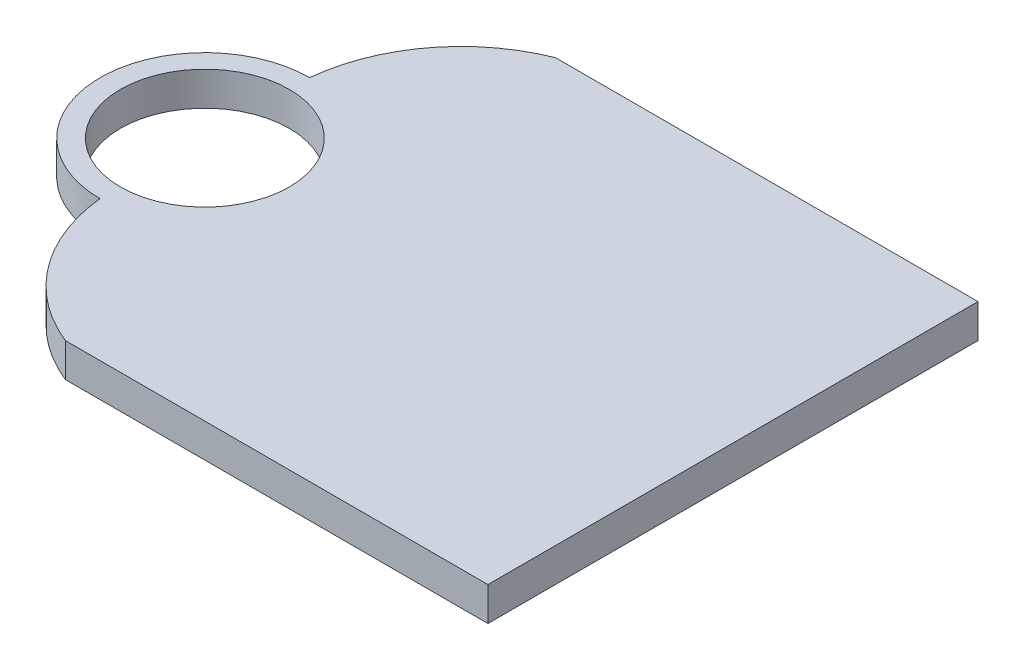
SolidWorks part; units mm, degrees
ref_plane "Front Plane" through (0, 0, 0) normal (0, 0, 1) x (1, 0, 0)
ref_plane "Top Plane" through (0, 0, 0) normal (0, 1, 0) x (1, 0, 0)
ref_plane "Right Plane" through (0, 0, 0) normal (1, 0, 0) x (0, 0, -1)
sketch "Sketch1" plane through (0, -22.822, 0) normal (0, 1, 0) x (1, 0, 0)
  line L0 (12.5, -29) -> (62.5, -29)
  line L1 (12.5, 0) -> (62.5, 0) construction
  line L2 (12.5, -29) -> (12.5, 29) construction
  line L3 (12.5, 29) -> (62.5, 29)
  line L4 (62.5, -29) -> (62.5, 29)
  line L5 (0, 9.9) -> (0, 0)
  line L6 (12.5, 0) -> (0, 0) construction
  arc A0 (0, 12.4) -> (0, -12.4) centre (0, 0) ccw
  circle A1 centre (0, 0) radius 9.9
  arc A2 (0, 12.4) -> (12.5, 29) centre (19.9018, 10.4201) cw
  arc A3 (0, -12.4) -> (12.5, -29) centre (19.9018, -10.4201) ccw
  circle M2 centre (0, 0) radius 10
  dimension "D1" = 19.8
  dimension "D2" = 24.8
  dimension "D5" = 20
  dimension "D3" = 50
  dimension "D4" = 29
  dimension "D6" = 12.5
extrude "Boss-Extrude1" add sketch "Sketch1" along normal blind 4 contours M2 | A0 A3 L0 L4 L3 A2 region at (-9.9717, -22.822, 0)
equation "\"D2@Sketch1\"=\"D1@Sketch1\"+5"
